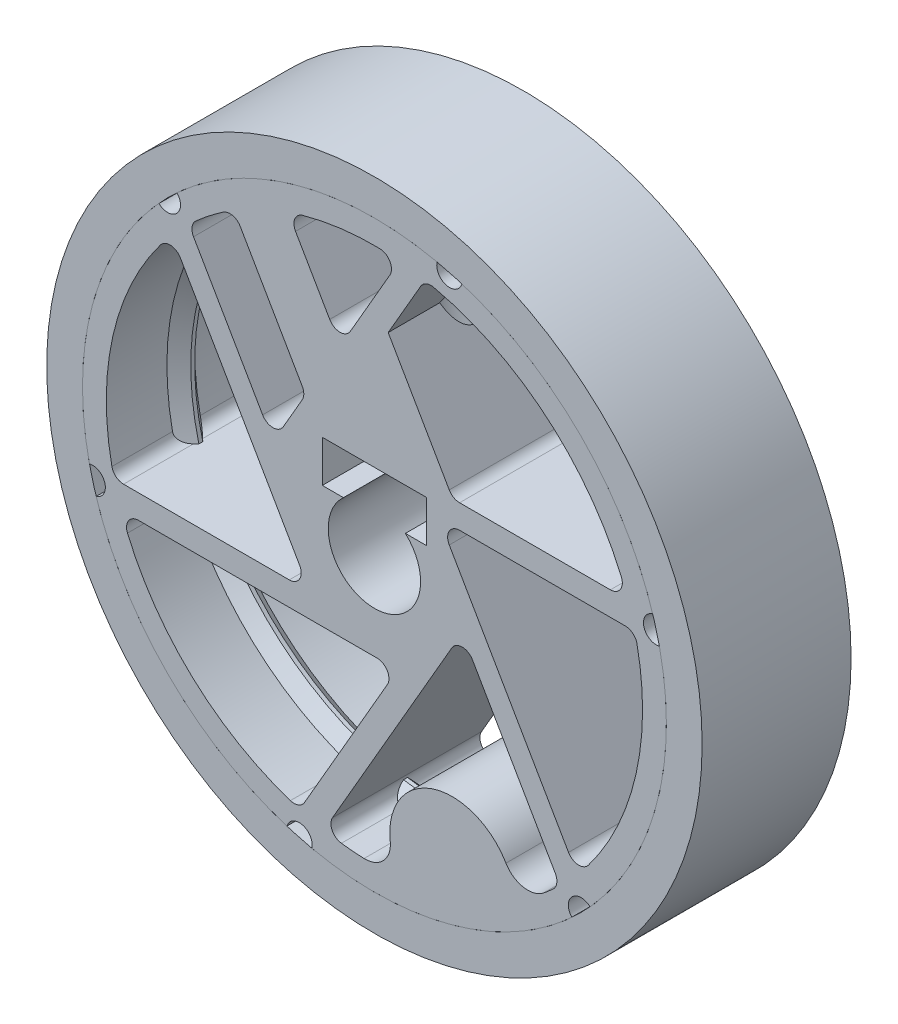
SolidWorks part; units mm, degrees
other "tire-mock"
other "hub"
ref_plane "Front Plane" through (0, 0, 0) normal (0, 0, 1) x (1, 0, 0)
ref_plane "Top Plane" through (0, 0, 0) normal (0, 1, 0) x (1, 0, 0)
ref_plane "Right Plane" through (0, 0, 0) normal (1, 0, 0) x (0, 0, -1)
other "Center of Mass"
sketch "Sketch1" plane through (0, 0, 0) normal (0, 0, 1) x (1, 0, 0)
  line L0 (2.0785, 2.3) -> (3.5, 2.3)
  line L1 (3.5, 2.3) -> (3.5, 5.1)
  line L2 (3.5, 5.1) -> (-3.5, 5.1)
  line L3 (-3.5, 5.1) -> (-3.5, 2.3)
  line L4 (-3.5, 2.3) -> (-2.0785, 2.3)
  line L5 (-1.9261, 2.3) -> (1.9261, 2.3) construction
  line L6 (-6.8127, 0) -> (-13.6123, 11.7773)
  line L7 (3.4064, -5.9) -> (6.8127, 0) construction
  line L8 (6.8127, 0) -> (3.4064, 5.9) construction
  line L9 (3.4064, 5.9) -> (-3.4064, 5.9) construction
  line L10 (-3.4064, 5.9) -> (-6.8127, 0) construction
  line L11 (-6.8127, 0) -> (-3.4064, -5.9) construction
  line L12 (-3.4064, -5.9) -> (3.4064, -5.9) construction
  line L13 (-3.4064, -5.9) -> (-17.0056, -5.9)
  line L14 (3.4064, -5.9) -> (-3.3932, -17.6773)
  line L15 (6.8127, 0) -> (13.6123, -11.7773)
  line L16 (-5.889, 1.6) -> (-12.4633, 12.9871) construction
  line L17 (5.889, -1.6) -> (12.4633, -12.9871)
  line L18 (1.5588, -5.9) -> (-5.0155, -17.2871)
  line L19 (-4.3301, -4.3) -> (-17.4788, -4.3)
  line L20 (3.4064, 5.9) -> (17.0056, 5.9) construction
  line L21 (4.3301, 4.3) -> (17.4788, 4.3)
  line L22 (-12.4633, 12.9871) -> (-6.8127, 3.2)
  line L23 (-6.8127, 3.2) -> (-3.3459, 9.2048)
  line L24 (-3.3459, 9.2048) -> (3.3459, 9.2048) construction
  line L25 (3.3459, 9.2048) -> (5.2539, 5.9)
  line L26 (5.2539, 5.9) -> (17.0056, 5.9)
  line L29 (-6.8127, 0) -> (-4.3301, -4.3)
  line L30 (-3.4064, -5.9) -> (1.5588, -5.9)
  line L31 (3.4064, -5.9) -> (5.889, -1.6)
  line L32 (6.8127, 0) -> (4.3301, 4.3)
  line L33 (-3.3459, 9.2048) -> (1.6863, 17.9208)
  line L34 (3.3932, 17.6773) -> (-1.4983, 9.2048)
  line L35 (3.3459, 9.2048) -> (-1.4983, 9.2048)
  line L36 (11.1297, 5.9) -> (11.1297, 4.3) construction
  line L37 (-0.8298, 13.5628) -> (0.5559, 12.7628) construction
  circle A0 centre (0, 0) radius 3 construction
  circle A1 centre (0, 0) radius 3.1 construction
  arc A2 (-2.0785, 2.3) -> (2.0785, 2.3) centre (0, 0) ccw
  circle A3 centre (0, 0) radius 5.9 construction
  circle A4 centre (0, 0) radius 22 construction
  circle A6 centre (0, 0) radius 19.6
  circle A7 centre (0, 0) radius 18 construction
  arc A8 (1.6863, 17.9208) -> (-12.4633, 12.9871) centre (0, 0) ccw
  arc A9 (-13.6123, 11.7773) -> (-17.4788, -4.3) centre (0, 0) ccw
  arc A10 (-5.0155, -17.2871) -> (-17.0056, -5.9) centre (0, 0) cw
  arc A11 (12.4633, -12.9871) -> (-3.3932, -17.6773) centre (0, 0) cw
  arc A12 (17.4788, 4.3) -> (13.6123, -11.7773) centre (0, 0) cw
  arc A13 (17.0056, 5.9) -> (3.3932, 17.6773) centre (0, 0) ccw
  point P13 (0, -3)
  point P43 (0, 9.2048)
  point P55 (-19.6, 0)
  point P56 (19.6, 0)
  point P58 (0, -19.6)
  point P59 (0, 19.6)
  point P61 (-18, 0)
  dimension "D1" = 6
  dimension "D7" = 44
  dimension "D3" = 7
  dimension "D4" = 2.8
  dimension "D5" = 5.3
  dimension "D6" = 0.8
  dimension "D10" = 1.6
  dimension "D11" = 4.1048
  dimension "D12" = 1.6
  dimension "D2" = 0.1
  dimension "D8" = 2.4
  dimension "D9" = 1.6
extrude "Boss-Extrude1" add sketch "Sketch1" along normal blind 10
ref_axis "Axis1" through (0, 0, 10) along (0, 0, -1)
sketch "Sketch9" plane through (0, 0, 0) normal (0, 0, -1) x (-1, 0, 0)
  line L0 (-3.3459, 9.2048) -> (-0.9238, 13.4)
  line L1 (-3.3459, 9.2048) -> (-5.2539, 5.9) construction
  line L2 (-3.3932, 17.6773) -> (1.4983, 9.2048) construction
  line L3 (-0.9238, 13.4) -> (1.4983, 9.2048)
  line L4 (1.4983, 9.2048) -> (-3.3459, 9.2048)
extrude "Boss-Extrude3" add sketch "Sketch9" against normal up to surface (10 mm away) up to face at (19.6, 0, 10)
sketch "Sketch10" plane through (0, 0, 0) normal (0, 0, -1) x (-1, 0, 0)
  line L0 (2.3094, 11) -> (6.6114, 18.4513)
  line L1 (3.3459, 9.2048) -> (-1.6863, 17.9208) construction
  line L2 (6.6114, 18.4513) -> (10.2298, 16.7186)
  line L3 (10.2298, 16.7186) -> (4.6188, 7)
  line L4 (4.6188, 7) -> (2.3094, 11)
  line L5 (-3.3459, 9.2048) -> (-5.2539, 5.9) construction
  circle A0 centre (0, 0) radius 19.6 construction
  dimension "D1" = 4
  dimension "D2" = 4
extrude "Boss-Extrude6" add sketch "Sketch10" against normal up to surface (10 mm away) up to face at (7.0386, 11.1752, 10)
fillet "Fillet1" radius 0.8 8 edges at (4.3301, 4.3, 5) (5.889, -1.6, 5) (1.5588, -5.9, 5) (-4.3301, -4.3, 5) (-6.8127, 3.2, 5) (5.2539, 5.9, 5) (-4.6188, 7, 5) (-2.3094, 11, 5)
fillet "Fillet2" radius 0.8 8 edges at (13.6123, -11.7773, 5) (17.0056, 5.9, 5) (-13.6123, 11.7773, 5) (-17.0056, -5.9, 5) (-3.3932, -17.6773, 5) (1.6863, 17.9208, 5) (-9.4295, 15.3324, 5) (-5.7971, 17.0409, 5)
fillet "Fillet3" radius 0.8 6 edges at (-17.4788, -4.3, 5) (-12.4633, 12.9871, 5) (17.4788, 4.3, 5) (12.4633, -12.9871, 5) (-5.0155, -17.2871, 5) (3.3932, 17.6773, 5)
sketch "Sketch8" [suppressed] plane through (0, 0, 10) normal (0, 0, 1) x (1, 0, 0)
  line L1 (-3.4613, 18.0715) -> (3.4613, 18.0715)
  line L2 (-3.4613, 18.0715) -> (-3.4613, 9.4048)
  line L3 (-3.4613, 9.4048) -> (3.4613, 9.4048)
  line L4 (3.4613, 18.0715) -> (3.4613, 9.4048)
  line L5 (0, 9.4048) -> (0, 18.0715) construction
  line L6 (-3.4613, 13.7382) -> (3.4613, 13.7382) construction
  circle A0 centre (0, 0) radius 18.4 construction
  point P0 (0, 13.7382)
extrude "Boss-Extrude2" [suppressed] add sketch "Sketch8" against normal up to surface (10 mm away) up to face at (-8.3312, 9.7549, 0)
sketch "Sketch2" plane through (0, 5.1, 0) normal (0, -1, 0) x (1, 0, 0)
  line L0 (0, 10) -> (0, 0) construction
  line L1 (3.5, 10) -> (-3.5, 10) construction
  line L2 (3.5, 0) -> (-3.5, 0) construction
  circle A0 centre (0, 5) radius 1.8
  dimension "D1" = 3.6
extrude "Cut-Extrude1" cut sketch "Sketch2" against normal up to surface (12.8098 mm away) up to face at (10.9125, 13.0451, 5)
sketch "Sketch5" plane through (0, 0, 0) normal (0, 1, 0) x (1, 0, 0)
  line L0 (-19.6, -3.6) -> (-19.6, -6.4)
  line L3 (-19.6, -3.6) -> (-18.8, -4.4)
  line L4 (-18.8, -4.4) -> (-18.8, -5.6)
  line L5 (-18.8, -5.6) -> (-19.6, -6.4)
  point P3 (-19.6, -5)
  dimension "D1" = 0.8
  dimension "D2" = 45
  dimension "D3" = 1.2
sketch "Sketch7" plane through (0, 0, 0) normal (0, 1, 0) x (1, 0, 0)
  line L0 (-19.6, -2.4686) -> (-19.6, -7.5314)
  line L1 (-19.6, -7.5314) -> (-17.2, -5.1314)
  line L2 (-17.2, -5.1314) -> (-17.2, -4.8686)
  line L3 (-17.2, -4.8686) -> (-19.6, -2.4686)
  line L4 (-18.8, -5.6) -> (-19.6, -6.4) construction
  line L5 (-19.6, -3.6) -> (-19.6, -6.4) construction
  line L6 (-18.8, -4.4) -> (-18.8, -5.6) construction
  point P6 (-19.6, -5)
  dimension "D1" = 1.6
  dimension "D2" = 0.8
revolve "Revolve1" add sketch "Sketch7" angle 360 about axis through (0, 0, 10) along (0, 0, -1)
sketch "Sketch6" plane through (0, 5.1, 0) normal (0, -1, 0) x (1, 0, 0)
  circle A0 centre (0, 5) radius 1.4
  dimension "D1" = 2.8
extrude "Cut-Extrude3" cut sketch "Sketch6" against normal through all
sketch "Sketch3" plane through (0, 0, 10) normal (0, 0, 1) x (1, 0, 0)
  line L0 (2.4826, -5.9) -> (-5.0457, -18.9394) construction
  line L1 (-3.4064, -5.9) -> (3.4064, -5.9) construction
  line L2 (1.5588, -5.9) -> (-5.0155, -17.2871) construction
  line L3 (1.5588, -5.9) -> (3.4064, -5.9) construction
  circle A0 centre (-5.0457, -18.9394) radius 0.8625
  circle A1 centre (0, 0) radius 19.6 construction
  circle A2 centre (0, 0) radius 18 construction
  circle A3 centre (-18.9249, -5.1) radius 0.8625
  circle A4 centre (-13.8792, 13.8394) radius 0.8625
  circle A5 centre (5.0457, 18.9394) radius 0.8625
  circle A6 centre (18.9249, 5.1) radius 0.8625
  circle A7 centre (13.8792, -13.8394) radius 0.8625
  point P14 (2.4826, -5.9)
  point P15 (-4.6145, -18.1925)
  point P16 (-4.2145, -17.4997)
  point P32 (0, 0)
  dimension "D1" = 0.8
  dimension "D2" = 6
extrude "Cut-Extrude2" cut sketch "Sketch3" against normal through all
revolve "Cut-Revolve2" cut sketch "Sketch5" angle 360 about axis through (0, 0, 10) along (0, 0, -1)
sketch "Sketch11" plane through (0, 0, 10) normal (0, 0, 1) x (1, 0, 0)
  circle A0 centre (0, 0) radius 22 construction
  circle A1 centre (0, 0) radius 22
  circle A2 centre (0, 0) radius 19.6 construction
  circle A3 centre (0, 0) radius 19.6
extrude "Boss-Extrude7" add sketch "Sketch11" against normal up to surface (10 mm away) separate body up to face at (-8.3312, 9.7549, 0)
sketch "Sketch12" plane through (0, 0, 0) normal (0, 0, -1) x (-1, 0, 0)
  line L1 (-3.4064, -5.9) -> (3.3932, -17.6773) construction
  line L2 (-5.889, -1.6) -> (-12.4633, -12.9871) construction
  circle A0 centre (-10.2973, -12.6355) radius 1.7 construction
  circle A2 centre (0.6281, -16.2879) radius 1.7 construction
  arc A3 (-12.4633, -12.9871) -> (3.3932, -17.6773) centre (0, 0) ccw construction
  arc A4 (-8.8307, -13.4951) -> (-1.0607, -16.0926) centre (-5.2191, -15.6119) cw
  arc A5 (-8.8307, -13.4951) -> (-11.3713, -13.9533) centre (-10.2973, -12.6355) cw
  arc A6 (-1.0607, -16.0926) -> (0.6936, -17.9866) centre (0.6281, -16.2879) ccw
  arc A7 (-11.3713, -13.9533) -> (0.6936, -17.9866) centre (0, 0) ccw
  point P18 (0, 0)
  point P20 (0, 0)
  point P21 (0, 0)
  point P22 (-5.2191, -15.6119)
  dimension "D1" = 3.4
extrude "Boss-Extrude8" add sketch "Sketch12" against normal up to surface (10 mm away) up to face at (0, 0, 10)
